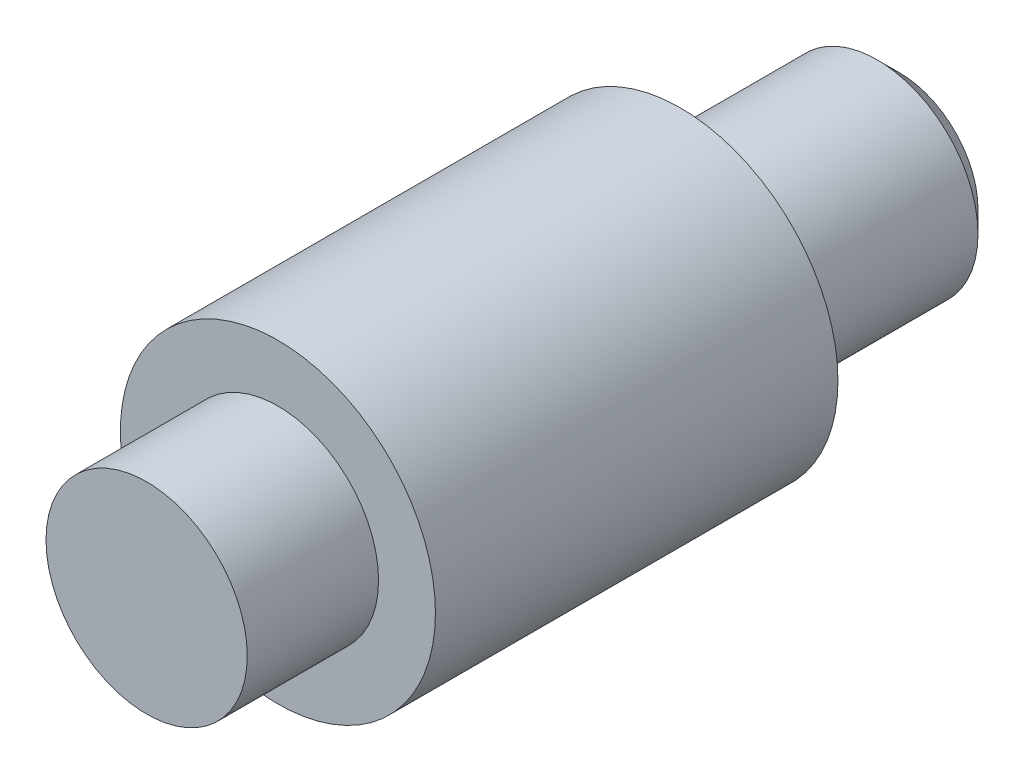
SolidWorks part; units mm, degrees
ref_plane "Front Plane" through (0, 0, 0) normal (0, 0, 1) x (1, 0, 0)
ref_plane "Top Plane" through (0, 0, 0) normal (0, 1, 0) x (1, 0, 0)
ref_plane "Right Plane" through (0, 0, 0) normal (1, 0, 0) x (0, 0, -1)
sketch "Sketch2" plane through (0, 0, 0) normal (0, 0, 1) x (1, 0, 0)
  circle A0 centre (0, 0) radius 1.25
  dimension "D1" = 2.5
sketch "Sketch3" plane through (0, 0, 0) normal (0, 0, 1) x (1, 0, 0)
  line L5 (-3.6, 3.6) -> (3.6, 3.6) construction
  line L6 (-3.6, 3.6) -> (-3.6, -3.6) construction
  line L7 (-3.6, -3.6) -> (3.6, -3.6) construction
  line L8 (3.6, 3.6) -> (3.6, -3.6) construction
  circle A0 centre (0, 0) radius 3.6
  point P4 (0, 3.6)
  point P6 (-3.6, 0)
  dimension "D1" = 7.2
extrude "Boss-Extrude1" add sketch "Sketch3" along normal blind 9.2
sketch "Sketch4" plane through (0, 0, 0) normal (0, 0, 1) x (1, 0, 0)
  circle A0 centre (0, 0) radius 2.3
  dimension "D1" = 4.6
extrude "Boss-Extrude2" add sketch "Sketch4" against normal blind 5
sketch "Sketch5" plane through (0, 0, 9.2) normal (0, 0, 1) x (1, 0, 0)
  circle A0 centre (0, 0) radius 2.3
  dimension "D1" = 4.6
extrude "Boss-Extrude3" add sketch "Sketch5" along normal blind 3
chamfer "Chamfer1" distance 0.5 angle 45 1 edges at (2.3, 0, -5)
equation "\"length\"=9.2"
equation "\"D1@Boss-Extrude1\"=\"length\""
equation "\"hole\"=4.6"
equation "\"D1@Sketch5\"=\"hole\""
equation "\"D1@Sketch4\"=\"hole\""
equation "\"foot\"=3"
equation "\"D1@Boss-Extrude3\"=\"foot\""
equation "\"D1@Boss-Extrude2\"=\"foot\"+2"
